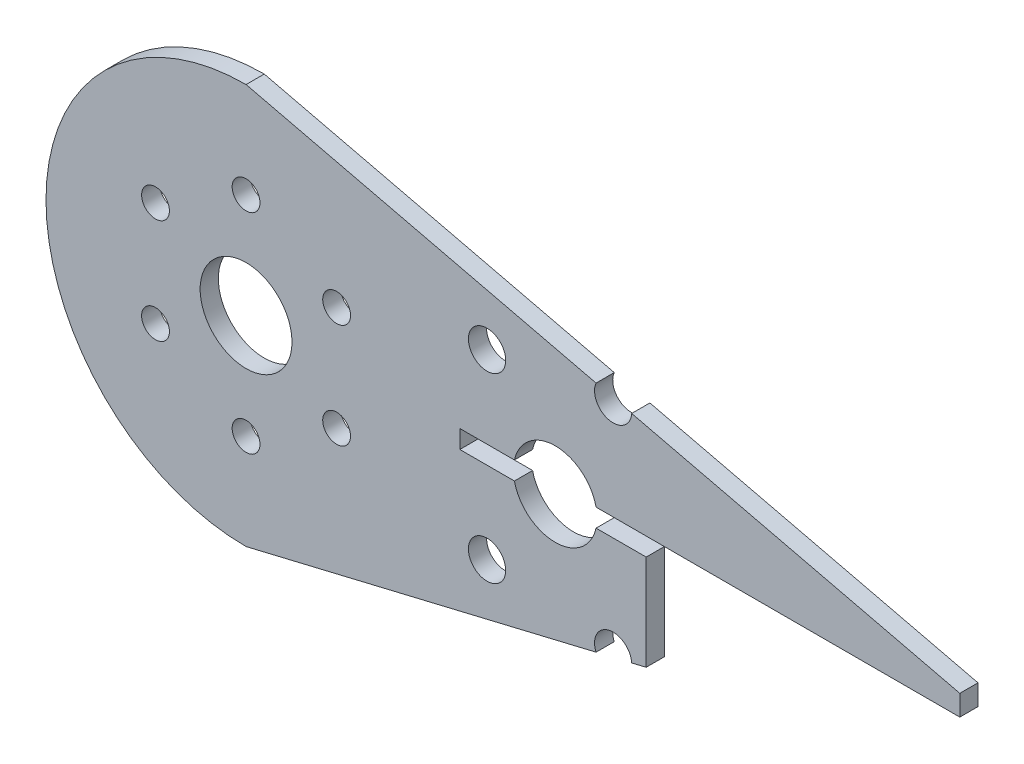
SolidWorks part; units mm, degrees
ref_plane "前视基准面" through (0, 0, 0) normal (0, 0, 1) x (1, 0, 0)
ref_plane "上视基准面" through (0, 0, 0) normal (0, 1, 0) x (1, 0, 0)
ref_plane "右视基准面" through (0, 0, 0) normal (1, 0, 0) x (0, 0, -1)
sketch "草图1" plane through (0, 0, 0) normal (0, 0, 1) x (1, 0, 0)
  line L0 (-38.999, 0) -> (5.001, 0) construction
  line L1 (-38.999, 22.002) -> (5.001, 22.002) construction
  line L6 (-38.999, 22.002) -> (-38.999, -22.002) construction
  line L7 (-38.999, -22.002) -> (5.001, -22.002) construction
  line L11 (5.001, 22.002) -> (5.001, -22.002) construction
  line L12 (5.001, 22.002) -> (5.001, 1) construction
  line L13 (-15.489, 1) -> (-9.489, 1)
  line L31 (-15.489, 1) -> (-15.489, -1)
  line L35 (-15.489, -1) -> (-9.489, -1)
  line L36 (-9.489, 1) -> (-9.489, -1) construction
  line L37 (5.001, 1) -> (-0.509, 1)
  line L39 (5.001, -1) -> (-0.509, -1)
  line L40 (-0.509, 1) -> (-0.509, -1) construction
  line L41 (5.001, -1) -> (5.001, -22.002) construction
  line L44 (5.001, 11.501) -> (5.001, 1) construction
  line L45 (5.001, -1) -> (5.001, -11.501)
  line L46 (5.001, 1) -> (39.4927, 1)
  line L47 (5.001, 11.501) -> (39.4927, 3.2692)
  line L48 (39.4927, 3.2692) -> (39.4927, 1)
  line L49 (-38.999, 22.002) -> (-0.509, 12.816)
  line L50 (3.4077, 11.8813) -> (5.001, 11.501)
  line L51 (-38.999, -22.002) -> (-0.509, -12.816)
  line L52 (3.4077, -11.8813) -> (5.001, -11.501)
  circle A3 centre (-38.999, 0) radius 5.05
  circle A6 centre (-38.999, 0) radius 11.5 construction
  circle A7 centre (-38.999, -11.5) radius 1.53
  circle A18 centre (-38.999, 0) radius 22.002 construction
  arc A35 (-38.999, 22.002) -> (-38.999, -22.002) centre (-38.999, 0) ccw
  circle A37 centre (-4.999, 0) radius 4.6 construction
  arc A38 (-0.509, 1) -> (-9.489, 1) centre (-4.999, 0) ccw
  arc A39 (-0.509, -1) -> (-9.489, -1) centre (-4.999, 0) cw
  circle A43 centre (-12.499, -10) radius 2.05
  circle A45 centre (-38.999, 0) radius 16.5 construction
  circle A47 centre (-48.9583, -5.75) radius 1.53
  circle A48 centre (-12.499, 10) radius 2.05
  circle A49 centre (-48.9583, 5.75) radius 1.53
  circle A50 centre (-38.999, 11.5) radius 1.53
  circle A51 centre (-29.0397, 5.75) radius 1.53
  circle A52 centre (-29.0397, -5.75) radius 1.53
  arc A53 (-0.509, 12.816) -> (3.4077, 11.8813) centre (1.3674, 12.0051) ccw
  arc A54 (-0.509, -12.816) -> (3.4077, -11.8813) centre (1.3674, -12.0051) cw
  point P45 (-61.001, 0)
  dimension "D3" = 10.1
  dimension "D4" = 44
  dimension "D5" = 9.2
  dimension "D6" = 10
  dimension "D7" = 23
  dimension "D8" = 3.06
  dimension "D9" = 2
  dimension "D11" = 33
  dimension "D2" = 44.004
  dimension "D10" = 6
  dimension "D16" = 6
extrude "凸台-拉伸1" add sketch "草图1" along normal blind 2
